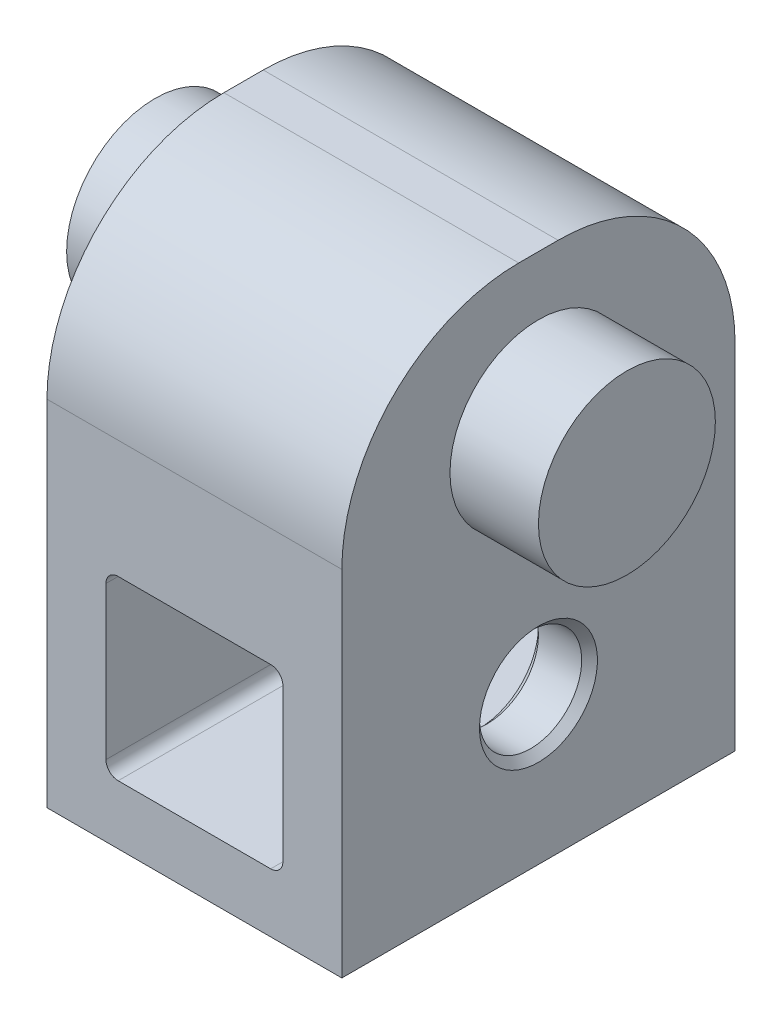
SolidWorks part; units mm, degrees
material "7075-O (SS)"
ref_plane "Front Plane" through (0, 0, 0) normal (0, 0, 1) x (1, 0, 0)
ref_plane "Top Plane" through (0, 0, 0) normal (0, 1, 0) x (1, 0, 0)
ref_plane "Right Plane" through (0, 0, 0) normal (1, 0, 0) x (0, 0, -1)
sketch "Sketch1" plane through (0, 0, 0) normal (0, 0, 1) x (1, 0, 0)
  line L1 (-37.5, -37.5) -> (37.5, -37.5)
  line L2 (-37.5, -37.5) -> (-37.5, 37.5)
  line L3 (-37.5, 37.5) -> (37.5, 37.5)
  line L4 (37.5, -37.5) -> (37.5, 37.5)
  line L5 (-37.5, -37.5) -> (37.5, 37.5) construction
  line L6 (-37.5, 37.5) -> (37.5, -37.5) construction
  point P0 (0, 0)
  dimension "D1" = 75
  dimension "D2" = 75
extrude "Boss-Extrude1" add sketch "Sketch1" along normal blind 100
sketch "Sketch5" plane through (0, 0, 100) normal (0, 0, 1) x (1, 0, 0)
  line L1 (-22.5, -22.5) -> (22.5, -22.5)
  line L2 (-22.5, -22.5) -> (-22.5, 22.5)
  line L3 (-22.5, 22.5) -> (22.5, 22.5)
  line L4 (22.5, -22.5) -> (22.5, 22.5)
  line L5 (-22.5, -22.5) -> (22.5, 22.5) construction
  line L6 (-22.5, 22.5) -> (22.5, -22.5) construction
  point P0 (0, 0)
  dimension "D1" = 45
  dimension "D2" = 45
extrude "Cut-Extrude2" cut sketch "Sketch5" against normal through all
fillet "Fillet2" radius 3.1 4 edges at (22.5, -22.5, 50) (22.5, 22.5, 50) (-22.5, 22.5, 50) (-22.5, -22.5, 50)
sketch "Sketch2" plane through (37.5, 0, 0) normal (1, 0, 0) x (0, 0, -1)
  line L0 (-100, 37.5) -> (0, 37.5)
  line L1 (0, 37.5) -> (0, 97.5)
  line L2 (0, 97.5) -> (-100, 97.5)
  line L3 (-100, 97.5) -> (-100, 37.5)
  dimension "D1" = 60
extrude "Boss-Extrude2" add sketch "Sketch2" against normal up to surface (75 mm away) up to face at (-37.5, 0, 50)
sketch "Sketch3" plane through (0, 0, 0) normal (1, 0, 0) x (0, 0, -1)
  line L0 (-50, 97.5) -> (-50, 22.5) construction
  line L4 (0, 22.5) -> (-100, 22.5) construction
  line L5 (-100, 97.5) -> (0, 97.5) construction
  circle A0 centre (-50, 60) radius 22.5
  point P8 (0, 0)
  point P9 (0, 0)
  point P10 (0, 0)
  point P11 (0, 0)
  point P12 (0, 0)
  dimension "D1" = 45
extrude "Hinge pins" add sketch "Sketch3" along normal mid plane 120
sketch "Sketch4" plane through (0, 0, 0) normal (-1, 0, 0) x (0, 0, 1)
  line L0 (50, 22.5) -> (50, -22.5) construction
  line L3 (0, 22.5) -> (100, 22.5) construction
  line L4 (100, -22.5) -> (0, -22.5) construction
  circle A0 centre (50, 0) radius 13
  point P2 (0, 0)
  point P3 (0, 0)
  point P8 (0, 0)
  point P9 (0, 0)
  dimension "D1" = 26
extrude "Cut-Extrude1" cut sketch "Sketch4" against normal through all both and the other way through all
chamfer "Chamfer1" distance 2 angle 45 4 edges at (-37.5, 0, 37) (37.5, 0, 63) (22.5, 0, 37) (-22.5, 0, 63)
fillet "Fillet4" radius 45 2 edges at (0, 97.5, 0) (0, 97.5, 100)
